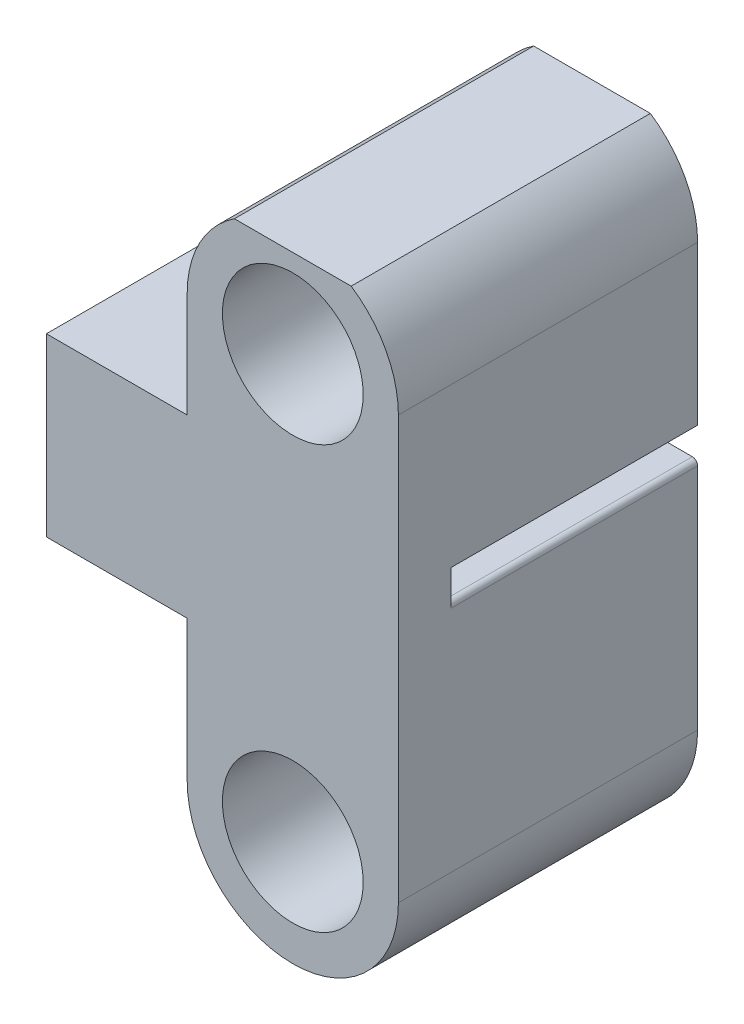
SolidWorks part; units mm, degrees
ref_plane "Front Plane" through (0, 0, 0) normal (0, 0, 1) x (1, 0, 0)
ref_plane "Top Plane" through (0, 0, 0) normal (0, 1, 0) x (1, 0, 0)
ref_plane "Right Plane" through (0, 0, 0) normal (1, 0, 0) x (0, 0, -1)
sketch "Sketch1" plane through (0, 0, 0) normal (0, 0, 1) x (1, 0, 0)
  line L0 (0, 0) -> (0, -12) construction
  line L1 (-3, 0) -> (-3, -12)
  line L2 (3, 0) -> (3, -12)
  arc A0 (3, 0) -> (-3, 0) centre (0, 0) ccw
  arc A1 (-3, -12) -> (3, -12) centre (0, -12) ccw
  circle A2 centre (0, 0) radius 2
  circle A3 centre (0, -12) radius 2
  dimension "D2" = 6
  dimension "D6" = 4
  dimension "D7" = 4
  dimension "D1" = 12
extrude "Boss-Extrude1" add sketch "Sketch1" along normal blind 8.5
sketch "Sketch2" plane through (3, 0, 0) normal (1, 0, 0) x (0, 0, -1)
  line L0 (-8.5, -6) -> (0, -6) construction
  line L1 (-8.5, -12) -> (-8.5, 0) construction
  line L2 (0, -12) -> (0, 0) construction
  line L3 (-4.25, 0) -> (-4.25, -12) construction
  line L4 (-8.5, 0) -> (0, 0) construction
  line L5 (-8.5, -12) -> (0, -12) construction
  circle A0 centre (-4.25, -8.5) radius 2
  dimension "D1" = 4
  dimension "D2" = 2.5
extrude "Cut-Extrude1" [suppressed] cut sketch "Sketch2" against normal through all
sketch "Sketch3" [suppressed] plane through (3, 0, 0) normal (1, 0, 0) x (0, 0, -1)
  line L1 (-0.6416, -8.5) -> (-2.4458, -5.375)
  line L2 (-2.4458, -5.375) -> (-6.0542, -5.375)
  line L3 (-6.0542, -5.375) -> (-7.8584, -8.5)
  line L4 (-7.8584, -8.5) -> (-6.0542, -11.625)
  line L5 (-6.0542, -11.625) -> (-2.4458, -11.625)
  line L6 (-2.4458, -11.625) -> (-0.6416, -8.5)
  line L7 (-1.8684, -4.375) -> (-6.6316, -4.375)
  line L8 (-6.6316, -4.375) -> (-9.0131, -8.5)
  line L9 (-9.0131, -8.5) -> (-6.6316, -12.625)
  line L10 (-6.6316, -12.625) -> (-1.8684, -12.625)
  line L11 (-1.8684, -12.625) -> (0.5131, -8.5)
  line L12 (0.5131, -8.5) -> (-1.8684, -4.375)
  circle A0 centre (-4.25, -8.5) radius 3.125 construction
  circle A1 centre (-4.25, -8.5) radius 4.125 construction
  dimension "D1" = 6.25
  dimension "D2" = 1
extrude "Boss-Extrude2" [suppressed] add sketch "Sketch3" along normal blind 2 and the other way blind 0.5
sketch "Sketch4" [suppressed] plane through (-3, 0, 0) normal (-1, 0, 0) x (0, 0, 1)
  line L0 (4.25, 0) -> (4.25, -6.5) construction
  line L1 (8.5, 0) -> (0, 0) construction
  line L3 (0.75, -2.75) -> (7.75, -2.75)
  line L4 (0.75, -2.75) -> (0.75, -5.75)
  line L5 (0.75, -5.75) -> (7.75, -5.75)
  line L6 (7.75, -2.75) -> (7.75, -5.75)
  line L7 (0.75, -2.75) -> (7.75, -5.75) construction
  line L8 (0.75, -5.75) -> (7.75, -2.75) construction
  circle A0 centre (4.25, -8.5) radius 2 construction
  point P7 (4.25, -4.25)
  dimension "D1" = 7
  dimension "D2" = 3
  dimension "D3" = 2.75
extrude "Cut-Extrude2" [suppressed] cut sketch "Sketch4" against normal through all
sketch "Sketch5" plane through (-3, 0, 0) normal (-1, 0, 0) x (0, 0, 1)
  line L0 (4.25, 0) -> (4.25, -12) construction
  line L1 (8.5, 0) -> (0, 0) construction
  line L2 (8.5, -12) -> (0, -12) construction
  line L3 (0, -6) -> (8.5, -6) construction
  line L4 (0, 0) -> (0, -12) construction
  line L5 (8.5, 0) -> (8.5, -12) construction
  line L7 (0, -15) -> (8.5, -15)
  line L8 (0, -15) -> (0, 3)
  line L9 (0, 3) -> (8.5, 3)
  line L10 (8.5, -15) -> (8.5, 3)
  line L11 (0, -15) -> (8.5, 3) construction
  line L12 (0, 3) -> (8.5, -15) construction
  point P12 (4.25, -6)
extrude "Cut-Extrude3" [suppressed] cut sketch "Sketch5" against normal through all flip side to cut
sketch "Sketch9" plane through (-3, 0, 0) normal (-1, 0, 0) x (0, 0, 1)
  line L0 (8.5, 0) -> (8.5, -12) construction
  line L1 (0, -3) -> (8.5, -3)
  line L2 (0, -3) -> (0, -8)
  line L3 (0, -8) -> (8.5, -8)
  line L4 (8.5, -3) -> (8.5, -8)
  line L5 (0, 0) -> (0, -12) construction
  line L6 (8.5, 0) -> (0, 0) construction
  dimension "D1" = 5
  dimension "D2" = 3
extrude "Boss-Extrude4" add sketch "Sketch9" along normal blind 4
sketch "Sketch6" plane through (3, 0, 0) normal (1, 0, 0) x (0, 0, -1)
  line L0 (0, -12) -> (0, 0) construction
  line L1 (0, -4.5) -> (-7, -4.5)
  line L2 (0, -4.5) -> (0, -6.1)
  line L3 (0, -6.1) -> (-7, -6.1)
  line L4 (-7, -4.5) -> (-7, -6.1)
  dimension "D1" = 1.6
  dimension "D2" = 4.5
  dimension "D3" = 7
extrude "Cut-Extrude5" cut sketch "Sketch6" against normal through all
sketch "Sketch7" plane through (0, 0, 7) normal (0, 0, -1) x (-1, 0, 0)
  line L0 (-3, -6.1) -> (-3, -5.5)
  line L1 (-3, -4.5) -> (-3, -6.1) construction
  line L2 (-2.85, -5.35) -> (-2.15, -5.35)
  line L3 (-2, -5.5) -> (-2, -6.1)
  line L4 (7, -6.1) -> (-3, -6.1) construction
  line L5 (-2, -6.1) -> (-3, -6.1)
  line L6 (-0.85, -5.35) -> (-0.15, -5.35)
  line L7 (0, -5.5) -> (0, -6.1)
  line L8 (0, -6.1) -> (-1, -6.1)
  line L9 (-1, -6.1) -> (-1, -5.5)
  line L10 (1.15, -5.35) -> (1.85, -5.35)
  line L11 (2, -5.5) -> (2, -6.1)
  line L12 (2, -6.1) -> (1, -6.1)
  line L13 (1, -6.1) -> (1, -5.5)
  line L14 (3.15, -5.35) -> (3.85, -5.35)
  line L15 (4, -5.5) -> (4, -6.1)
  line L16 (4, -6.1) -> (3, -6.1)
  line L17 (3, -6.1) -> (3, -5.5)
  line L18 (5.15, -5.35) -> (5.85, -5.35)
  line L19 (6, -5.5) -> (6, -6.1)
  line L20 (6, -6.1) -> (5, -6.1)
  line L21 (5, -6.1) -> (5, -5.5)
  arc A0 (-2.15, -5.35) -> (-2, -5.5) centre (-2.15, -5.5) cw
  arc A1 (-3, -5.5) -> (-2.85, -5.35) centre (-2.85, -5.5) cw
  arc A2 (-1, -5.5) -> (-0.85, -5.35) centre (-0.85, -5.5) cw
  arc A3 (-0.15, -5.35) -> (0, -5.5) centre (-0.15, -5.5) cw
  arc A4 (1, -5.5) -> (1.15, -5.35) centre (1.15, -5.5) cw
  arc A5 (1.85, -5.35) -> (2, -5.5) centre (1.85, -5.5) cw
  arc A6 (3, -5.5) -> (3.15, -5.35) centre (3.15, -5.5) cw
  arc A7 (3.85, -5.35) -> (4, -5.5) centre (3.85, -5.5) cw
  arc A8 (5, -5.5) -> (5.15, -5.35) centre (5.15, -5.5) cw
  arc A9 (5.85, -5.35) -> (6, -5.5) centre (5.85, -5.5) cw
  point P11 (-2, -5.35)
  point P14 (-3, -5.35)
  dimension "D3" = 0.15
  dimension "D1" = 1
  dimension "D2" = 0.75
  dimension "D4" = 5
extrude "Boss-Extrude3" add sketch "Sketch7" along normal through all
sketch "Sketch10" plane through (0, 0, 8.5) normal (0, 0, 1) x (1, 0, 0)
  line L1 (-2.5, 3.5) -> (2.5, 3.5)
  line L2 (-2.5, 3.5) -> (-2.5, 2.5)
  line L3 (-2.5, 2.5) -> (2.5, 2.5)
  line L4 (2.5, 3.5) -> (2.5, 2.5)
  line L5 (-2.5, 3.5) -> (2.5, 2.5) construction
  line L6 (-2.5, 2.5) -> (2.5, 3.5) construction
  arc A0 (3, 0) -> (-3, 0) centre (0, 0) ccw construction
  point P0 (0, 3)
  dimension "D1" = 1
  dimension "D2" = 5
extrude "Cut-Extrude6" cut sketch "Sketch10" against normal through all
equation "\"X-ROD-SPACING\"=45"
equation "\"Y-ROD-SPACING\"=75"
equation "\"Z-ROD-SPACING\"=17.5"
equation "\"Y-BED-OFFSET\"=2"
equation "\"Y-BED-ROD-INSET\"=3.5"
equation "\"Y-BED-SCREW-SPACING\"=209"
equation "\"Y-BED-SCREW-CUTOUT-SLOT-HEIGHT\"=2"
equation "\"T-SLOT-NUT-FILLET-RADIUS\"=0.25"
equation "\"T-SLOT-SCREW-SHAFT-RADIUS\"=1.75"
equation "\"T-SLOT-SCREW-SHAFT-CUTOUT-LENGTH\"=10.5"
equation "\"T-SLOT-NUT-DEPTH\"=4.2"
equation "\"T-SLOT-NUT-WIDTH\"=3"
equation "\"T-SLOT-NUT-END-DISTANCE\"=8"
equation "\"ACRYLIC-THICKNESS\"=10"
equation "\"ACRYLIC-THICKNESS2\"=4.5"
equation "\"ACRYLIC-TAB-CUTOUT-SIZE\"=\"ACRYLIC-THICKNESS\"+\"ACRYLIC-TAB-TOLERANCE\"*2"
equation "\"ACRYLIC-TAB-TOLERANCE\"=.1"
equation "\"ACRYLIC-TAB-WIDTH\"=\"ACRYLIC-THICKNESS\""
equation "\"ACRYLIC-M3-HOLE\"=3.1"
equation "\"SMOOTHROD-CAP-SCREW-DISTANCE\"=20"
equation "\"FRAME-WIDTH-INNER\"=370"
equation "\"NEMA17-HOLE-SPACING\"=31"
equation "\"NEMA17-CENTRAL-CUTOUT\"=22.5"
equation "\"Z-BRACKET-REACH\"=55"
equation "\"Z-ROD-INSET\"=16"
equation "\"TOP-BRACKET-SPACING\"=40"
equation "\"SMOOTHROD-X-LENGTH\"=350"
equation "\"SMOOTHROD-Y-LENGTH\"=350"
equation "\"SMOOTHROD-Z-LENGTH\"=350"
equation "\"SMOOTHROD-TIGHTENING-HEADROOM\"=.25"
equation "\"LEADSCREW-Z-LENGTH\"=300"
equation "\"SCREW-LENGTH-FRAME\"=\"ACRYLIC-THICKNESS\" + 10"
equation "\"SCREW-LENGTH-MOTOR\"=\"ACRYLIC-THICKNESS\" + 5"
equation "\"SCREW-LENGTH-EXTRUDER\"=28"
equation "\"SCREW-HEAD-RADIUS\"=6"
equation "\"PRINTED-M3-HOLE\"=3.5"
equation "\"PRINTED-X-SMOOTHROD-DIAMETER\"=8.2"
equation "\"PRINTED-X-SMOOTHROD-CUTOUT\"=10"
equation "\"PRINTED-X-BASE-HEIGHT\"=10"
equation "\"PRINTED-LM8UU-CUTOUT-SIZE\"=15.25"
equation "\"PRINTED-LM8UU-CUTOUT-LENGTH\"=24.5"
equation "\"PRINTED-X-IDLER-HEIGHT\"=16"
equation "\"PRINTED-M3-NUT-AF\"=6.25"
equation "\"PSU-MOUNTING-WIDTH\"=95"
equation "\"PSU-MOUNTING-HEIGHT\"=177"
equation "\"Y-BELT-TO-ROD-DISTANCE\"=20"
equation "\"SPOOL-HOLDER-ROD-SPACING\"=150"
equation "\"ACRYLIC-X-CARRIAGE-WIDTH\"=55"
equation "\"ACRYLIC-X-CARRIAGE-HEIGHT\"=75"
equation "\"ACRYLIC-X-CARRIAGE-LM8UU-CUTOUT-WIDTH\"=24.25"
equation "\"ACRYLIC-X-CARRIAGE-LM8UU-CUTOUT-HEIGHT\"=11.5"
equation "\"ACRYLIC-X-CARRIAGE-SCREW-SPACING-X\"=15"
equation "\"ACRYLIC-X-CARRIAGE-SCREW-SPACING-Y\"=33"
equation "\"ACRYLIC-X-CARRIAGE-CENTER-TAB-SPACING\"=14"
equation "\"ACRYLIC-X-CARRIAGE-EXTRUDER-OFFSET\"=26"
equation "\"ACRYLIC-X-CARRIAGE-EXTRUDER-ANGLE\"=90"
equation "\"ACRYLIC-X-CARRIAGE-EXTRUDER-SHELF-DEPTH\"=\"ACRYLIC-X-CARRIAGE-EXTRUDER-OFFSET\" + 28"
equation "\"ACRYLIC-X-CARRIAGE-EXTRUDER-BRACE-SPACING\"=23"
equation "\"ACRYLIC-X-CARRIAGE-EXTRUDER-BRACE-TAB-OFFSET\"=20"
equation "\"ACRYLIC-X-CARRIAGE-EXTRUDER-BRACE-HEIGHT\"=35"
equation "\"ACRYLIC-X-CARRIAGE-EXTRUDER-BRACE-SCREW-SPACING\"=22"
equation "\"ACRYLIC-X-CARRIAGE-DUAL-WIDTH-MULTIPLIER\"=1.65"
equation "\"ACRYLIC-X-CARRIAGE-DUAL-HOTEND-SPACING\"=42"
equation "\"ACRYLIC-X-CARRIAGE-DUAL-WIDTH\"=103"
equation "\"ACRYLIC-X-CARRIAGE-DUAL-HOTEND-SEPARATION\"=35"
equation "\"ACRYLIC-X-CARRIAGE-DUAL-MOUNT-PLATE-DEPTH\"=76"
equation "\"ACRYLIC-X-CARRIAGE-DUAL-MOUNT-BRACE-WIDTH\"=45"
equation "\"ACRYLIC-X-CARRIAGE-DUAL-MOUNT-SCREW-WIDTH\"=40"
equation "\"BLOWER-FAN-WIDTH\"=15"
equation "\"D1@Sketch3\"=\"PRINTED-M3-NUT-AF\""
